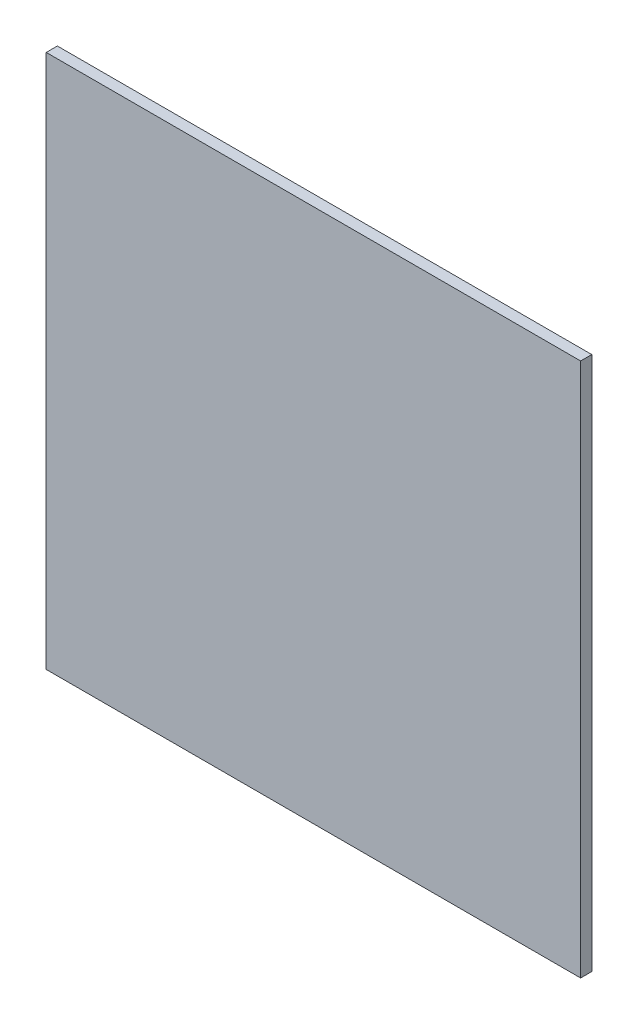
SolidWorks part; units mm, degrees
material "Custom Plastic"
ref_plane "X-Y Datum" through (0, 0, 0) normal (0, 0, 1) x (1, 0, 0)
ref_plane "X-Z Datum" through (0, 0, 0) normal (0, 1, 0) x (1, 0, 0)
ref_plane "Y-Z Datum" through (0, 0, 0) normal (1, 0, 0) x (0, 0, -1)
sketch "Sketch2" plane through (0, 0, 0) normal (0, 0, 1) x (1, 0, 0)
  line L1 (-152.4, 152.4) -> (152.4, 152.4)
  line L2 (-152.4, 152.4) -> (-152.4, -152.4)
  line L3 (-152.4, -152.4) -> (152.4, -152.4)
  line L4 (152.4, 152.4) -> (152.4, -152.4)
  line L5 (-152.4, 152.4) -> (152.4, -152.4) construction
  line L6 (-152.4, -152.4) -> (152.4, 152.4) construction
  point P0 (0, 0)
  dimension "D1" = 304.8
  dimension "D2" = 304.8
extrude "Boss-Extrude1" add sketch "Sketch2" along normal blind 6.35
